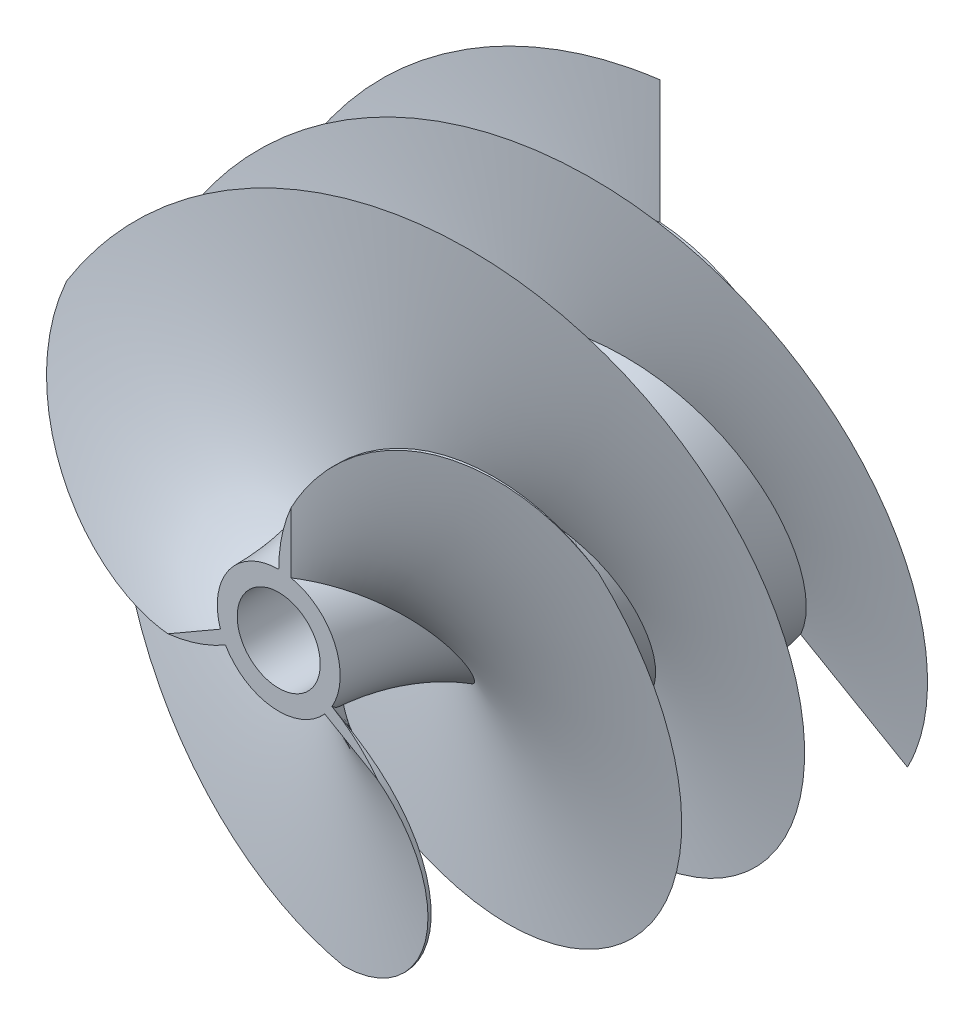
SolidWorks part; units mm, degrees
material "Titanium"
ref_plane "Front Plane" through (0, 0, 0) normal (1, 0, 0) x (0, 1, 0)
ref_plane "Top Plane" through (0, 0, 0) normal (0, 0, 1) x (0, 1, 0)
ref_plane "Right Plane" through (0, 0, 0) normal (0, 1, 0) x (-1, 0, 0)
sketch "Sketch2" plane through (0, 0, 0) normal (1, 0, 0) x (0, 1, 0)
  line L0 (-3.3782, 0) -> (-3.3782, 30)
  line L1 (-3.3782, 30) -> (-5, 30)
  line L2 (-15, 0) -> (-3.3782, 0)
  line L3 (0, 0) -> (0, 30) construction
  line L4 (-25, 0) -> (-25, 30) construction
  line L5 (-15, 0) -> (-15, 30) construction
  arc A0 (-5, 30) -> (-10, 15) centre (-30, 30) cw
  arc A1 (-10, 15) -> (-15, 0) centre (10, 0) ccw
  point P7 (0, 0)
  point P13 (-10.8814, 12.3557)
  dimension "D1" = 30
  dimension "D2" = 25
  dimension "D3" = 15
  dimension "D4" = 6.7564
  dimension "D5" = 5
ref_axis "Axis1" through (0, 0, 31.5) along (0, 0, -1)
revolve "Revolve1" add sketch "Sketch2" angle 360 about axis through (0, 0, 31.5) along (0, 0, -1)
sketch "Sketch3" plane through (0, 0, 30) normal (0, 0, -1) x (1, 0, 0)
  circle A0 centre (0, 0) radius 25
  dimension "D1" = 50
curve "Helix/Spiral1" pitch 30 height 30 radius 25 centre (0, 0, 30) axis (0, 0, -1) start towards (0, 1, 0)
sketch "Sketch4" plane through (0, 0, 30) normal (0, 0, 1) x (1, 0, 0)
  line L1 (21.3035, 13.0828) -> (28.1101, 5.4042) construction
  line L2 (1, 25) -> (1, 3.3782)
  line L7 (0, 0) -> (1, 0)
  line L9 (21.3035, 13.0828) -> (26.9244, 3.93) construction
  line L10 (0, 0) -> (21.3035, 13.0828) construction
  line L11 (0, 18.755) -> (0, 3.3782)
  line L12 (0, 3.3782) -> (1, 3.3782)
  arc A0 (1, 25) -> (0, 18.755) centre (20, 18.755) ccw
  arc A1 (0, 5) -> (21.3035, 13.0828) centre (12.1851, 5) cw construction
  circle A2 centre (0, 0) radius 5 construction
  circle A5 centre (0, 0) radius 3.3782 construction
  point P14 (0, 0)
  point P22 (0, 18.3319)
  point P23 (21.2715, 13.1444)
  point P24 (0, 0)
  point P25 (0.1431, 4.998)
  point P26 (0, 0)
  dimension "D3" = 1
  dimension "D4" = 20
  dimension "D5" = 10
  dimension "D1" = 25
  dimension "D2" = 25
sweep "Sweep2" add profiles "Sketch4" path "Helix/Spiral1"
sketch "Sketch6" plane through (0, 0, 30) normal (0, 0, 1) x (1, 0, 0)
  line L0 (0, 0) -> (21.3035, 13.0828) construction
  line L1 (0, 5) -> (-29.5804, 5)
  line L2 (0, 18.755) -> (0, 5) construction
  line L3 (21.3035, 13.0828) -> (26.3653, 7.3725) construction
  line L4 (21.3035, 13.0828) -> (25.6059, 6.0771) construction
  line L5 (21.3035, 13.0828) -> (25.5642, 15.6994)
  arc A0 (0, 5) -> (21.3035, 13.0828) centre (12.1851, 5) cw
  arc A2 (25.5642, 15.6994) -> (-29.5804, 5) centre (0, 0) ccw
  point P7 (24.2313, 17.5916)
  point P10 (0, 0)
  point P13 (22.5439, 19.7932)
  dimension "D1" = 25
  dimension "D2" = 10
  dimension "D3" = 5
extrude "Cut-Extrude1" cut sketch "Sketch6" against normal blind 10 contours L1 A2 L5 A0
pattern_circular "CirPattern4" count 3 over 360 about axis through (0, 0, 31.5) along (0, 0, -1) of bodies 108
revolve "Revolve3" add sketch "Sketch2<3>" angle 360 about axis through (0, 0, 31.5) along (0, 0, -1)
sketch "Sketch2<3>" plane through (0, 0, 0) normal (1, 0, 0) x (0, 1, 0) same geometry as "Sketch2"
sketch "Sketch7" plane through (0, 0, 0) normal (0, 0, -1) x (1, 0, 0)
  line L0 (-7.5, 0) -> (7.5, 0) construction
  line L1 (0, -7.5) -> (0, 7.5) construction
  circle A0 centre (0, 7.5) radius 1.1906
  circle A1 centre (7.5, 0) radius 1.1906
  circle A2 centre (0, -7.5) radius 1.1906
  circle A3 centre (-7.5, 0) radius 1.1906
  point P8 (-8.8644, 0)
  dimension "D1" = 2.3812
  dimension "D2" = 15
extrude "Cut-Extrude2" cut sketch "Sketch7" against normal blind 5
